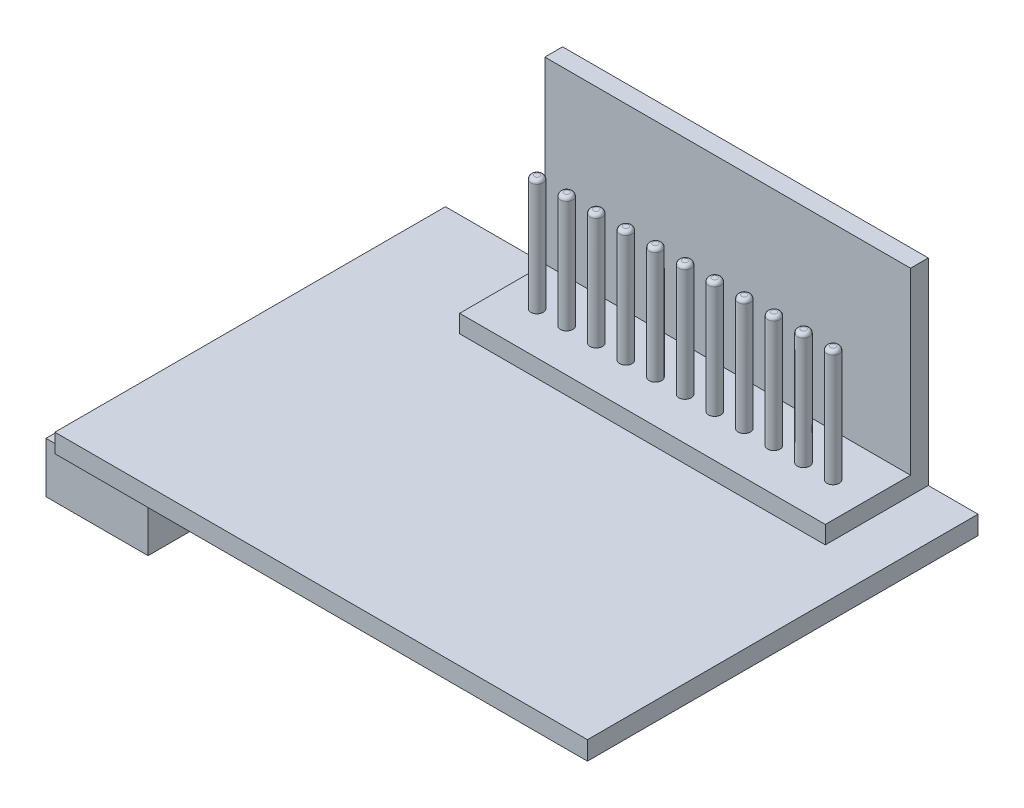
SolidWorks part; units mm, degrees
ref_plane "Front" through (0, 0, 0) normal (0, 0, 1) x (1, 0, 0)
ref_plane "Top" through (0, 0, 0) normal (0, 1, 0) x (1, 0, 0)
ref_plane "Right" through (0, 0, 0) normal (1, 0, 0) x (0, 0, -1)
sketch "Sketch1" plane through (0, 0, 0) normal (0, 1, 0) x (1, 0, 0)
  line L1 (0, 0) -> (30, 0)
  line L2 (0, 0) -> (0, 22)
  line L3 (0, 22) -> (30, 22)
  line L4 (30, 0) -> (30, 22)
  dimension "D1" = 30
  dimension "D2" = 22
extrude "Boss-Extrude1" add sketch "Sketch1" along normal blind 1.05
sketch "Sketch2" plane through (0, 1.05, 0) normal (0, 1, 0) x (1, 0, 0)
  line L0 (30, 22) -> (0, 22) construction
  line L1 (6.6, 22) -> (27.2, 22)
  line L2 (6.6, 22) -> (6.6, 16.2)
  line L3 (6.6, 16.2) -> (27.2, 16.2)
  line L4 (27.2, 22) -> (27.2, 16.2)
  line L6 (0, 22) -> (0, 0) construction
  dimension "D1" = 6.6
  dimension "D2" = 20.6
  dimension "D3" = 5.8
extrude "Boss-Extrude2" add sketch "Sketch2" along normal blind 11.1
sketch "Sketch4" plane through (0, 0, 0) normal (0, -1, 0) x (1, 0, 0)
  line L0 (30, -22) -> (0, -22) construction
  line L1 (-1, -0.5) -> (4.75, -0.5)
  line L2 (-1, -0.5) -> (-1, -16)
  line L3 (-1, -16) -> (4.75, -16)
  line L4 (4.75, -0.5) -> (4.75, -16)
  line L5 (0, -22) -> (0, 0) construction
  dimension "D1" = 6
  dimension "D2" = 15.5
  dimension "D3" = 5.75
  dimension "D4" = 1
extrude "Boss-Extrude3" add sketch "Sketch4" along normal blind 2.85
sketch "Sketch5" plane through (0, 0, -16.2) normal (0, 0, 1) x (1, 0, 0)
  line L0 (27.2, 12.15) -> (27.2, 1.05) construction
  line L1 (6.6, 12.15) -> (27.2, 12.15)
  line L2 (6.6, 12.15) -> (6.6, 2.05)
  line L3 (6.6, 2.05) -> (27.2, 2.05)
  line L4 (27.2, 12.15) -> (27.2, 2.05)
  line L5 (6.6, 1.05) -> (27.2, 1.05) construction
  dimension "D1" = 1
extrude "Cut-Extrude1" cut sketch "Sketch5" against normal offset from surface (4.8 mm away) 1 up to face at (16.5375, 4.95, -22)
sketch "Sketch6" plane through (0, 2.05, 0) normal (0, 1, 0) x (1, 0, 0)
  line L0 (6.6, 18.6) -> (27.2, 18.6) construction
  line L1 (6.6, 21) -> (6.6, 16.2) construction
  line L2 (27.2, 21) -> (27.2, 16.2) construction
  line L3 (16.9, 21) -> (16.9, 16.2) construction
  line L4 (27.2, 21) -> (6.6, 21) construction
  line L5 (6.6, 16.2) -> (27.2, 16.2) construction
  circle A0 centre (8.5609, 18.6) radius 0.35
  circle A1 centre (10.2287, 18.6) radius 0.35
  circle A2 centre (11.8965, 18.6) radius 0.35
  circle A3 centre (13.5644, 18.6) radius 0.35
  circle A4 centre (15.2322, 18.6) radius 0.35
  circle A5 centre (16.9, 18.6) radius 0.35
  circle A6 centre (18.5678, 18.6) radius 0.35
  circle A7 centre (20.2356, 18.6) radius 0.35
  circle A8 centre (21.9035, 18.6) radius 0.35
  circle A9 centre (23.5713, 18.6) radius 0.35
  circle A10 centre (25.2391, 18.6) radius 0.35
  dimension "D1" = 0.7
  dimension "D2" = 11
extrude "Boss-Extrude4" add sketch "Sketch6" along normal blind 6.52
fillet "Fillet1" radius 0.2 11 edges at (25.2391, 8.57, -18.25) (23.5713, 8.57, -18.25) (21.9035, 8.57, -18.25) (20.2356, 8.57, -18.25) (18.5678, 8.57, -18.25) (16.9, 8.57, -18.25) (15.2322, 8.57, -18.25) (13.5644, 8.57, -18.25) (11.8965, 8.57, -18.25) (10.2287, 8.57, -18.25) (8.5609, 8.57, -18.25)
